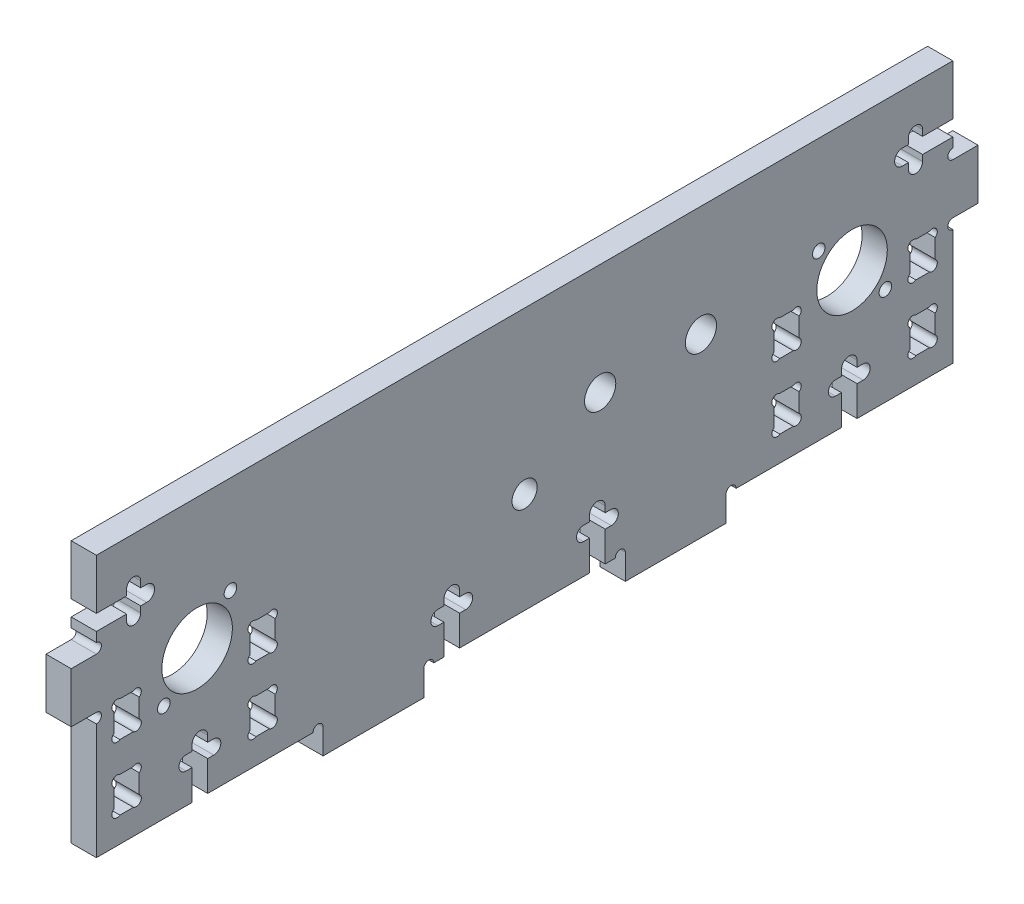
SolidWorks part; units mm, degrees
ref_plane "정면" through (0, 0, 0) normal (0, 0, 1) x (1, 0, 0)
ref_plane "윗면" through (0, 0, 0) normal (0, 1, 0) x (1, 0, 0)
ref_plane "우측면" through (0, 0, 0) normal (1, 0, 0) x (0, 0, -1)
sketch "스케치1" plane through (0, 0, 0) normal (1, 0, 0) x (0, 0, -1)
  line L1 (0, 0) -> (170, 0)
  line L2 (0, 0) -> (0, 52)
  line L3 (0, 52) -> (170, 52)
  line L4 (170, 0) -> (170, 52)
  dimension "D1" = 170
  dimension "D2" = 52
extrude "보스-돌출1" add sketch "스케치1" along normal blind 5
sketch "스케치2" plane through (5, 0, 0) normal (1, 0, 0) x (0, 0, -1)
  line L0 (170, 26) -> (150, 26) construction
  line L1 (170, 0) -> (170, 52) construction
  line L2 (150, 26) -> (20, 26) construction
  line L3 (20, 26) -> (0, 26) construction
  line L4 (0, 52) -> (0, 0) construction
  circle A0 centre (150, 26) radius 7
  circle A1 centre (20, 26) radius 7
  dimension "D2" = 14
  dimension "D1" = 20
extrude "컷-돌출1" cut sketch "스케치2" against normal blind 10
sketch "스케치3" plane through (5, 0, 0) normal (1, 0, 0) x (0, 0, -1)
  line L0 (0, 0) -> (170, 0) construction
  line L1 (45, 0) -> (65, 0)
  line L2 (45, 0) -> (45, -5)
  line L3 (45, -5) -> (65, -5)
  line L4 (65, 0) -> (65, -5)
  line L5 (0, -5) -> (45, -5) construction
  line L6 (65, -5) -> (105, -5) construction
  line L7 (125, 0) -> (105, 0)
  line L8 (125, 0) -> (125, -5)
  line L9 (125, -5) -> (105, -5)
  line L10 (105, 0) -> (105, -5)
  line L11 (125, -5) -> (170, -5) construction
  line L12 (170, -5) -> (170, 0) construction
  line L13 (0, 0) -> (0, -5) construction
  line L14 (0, 0) -> (0, -5) construction
  line L15 (0, -5) -> (45, -5) construction
  dimension "D1" = 45
  dimension "D2" = 20
extrude "보스-돌출2" add sketch "스케치3" against normal blind 5
sketch "스케치6" plane through (5, 0, 0) normal (1, 0, 0) x (0, 0, -1)
  line L0 (151, 0) -> (151, 6)
  line L1 (147.9, 10) -> (151, 10) construction
  line L2 (146.7, 6) -> (146.7, 8.8) construction
  line L3 (151, 6) -> (151, 8.8) construction
  line L4 (147.9, 0) -> (151, 0)
  line L5 (146.7, 8.8) -> (147.9, 8.8)
  line L6 (147.9, 0) -> (147.9, 6)
  line L7 (152.2, 8.8) -> (152.2, 6) construction
  line L8 (147.9, 6) -> (146.7, 6)
  line L9 (147.9, 8.8) -> (147.9, 6) construction
  line L10 (151, 8.8) -> (151, 10)
  line L11 (147.9, 6) -> (151, 6) construction
  line L12 (147.9, 8.8) -> (151, 8.8) construction
  line L13 (151, 8.8) -> (152.2, 8.8)
  line L14 (147.9, 8.8) -> (147.9, 10)
  line L15 (149.45, 10) -> (149.45, 12.1831) construction
  line L16 (152.2, 6) -> (151, 6)
  line L18 (65, 0) -> (105, 0) construction
  line L19 (101, 0) -> (101, 6)
  line L20 (97.9, 10) -> (101, 10) construction
  line L21 (96.7, 6) -> (96.7, 8.8) construction
  line L22 (101, 6) -> (101, 8.8) construction
  line L23 (97.9, 0) -> (101, 0)
  line L24 (96.7, 8.8) -> (97.9, 8.8)
  line L25 (97.9, 0) -> (97.9, 6)
  line L26 (102.2, 8.8) -> (102.2, 6) construction
  line L27 (97.9, 6) -> (96.7, 6)
  line L28 (97.9, 8.8) -> (97.9, 6) construction
  line L29 (101, 8.8) -> (101, 10)
  line L30 (97.9, 6) -> (101, 6) construction
  line L31 (97.9, 8.8) -> (101, 8.8) construction
  line L32 (101, 8.8) -> (102.2, 8.8)
  line L33 (97.9, 8.8) -> (97.9, 10)
  line L34 (99.45, 10) -> (99.45, 12.1831) construction
  line L35 (102.2, 6) -> (101, 6)
  line L37 (105, 0) -> (105, -5) construction
  line L71 (85, 52) -> (85, 0) construction
  line L72 (170, 52) -> (0, 52) construction
  line L89 (70.55, 10) -> (70.55, 12.1831) construction
  line L90 (72.1, 8.8) -> (69, 8.8) construction
  line L91 (72.1, 6) -> (69, 6) construction
  line L92 (72.1, 8.8) -> (72.1, 6) construction
  line L93 (67.8, 8.8) -> (67.8, 6) construction
  line L94 (69, 6) -> (69, 8.8) construction
  line L95 (73.3, 6) -> (73.3, 8.8) construction
  line L96 (72.1, 10) -> (69, 10) construction
  line L97 (20.55, 10) -> (20.55, 12.1831) construction
  line L98 (22.1, 8.8) -> (19, 8.8) construction
  line L99 (22.1, 6) -> (19, 6) construction
  line L100 (22.1, 8.8) -> (22.1, 6) construction
  line L101 (17.8, 8.8) -> (17.8, 6) construction
  line L102 (19, 6) -> (19, 8.8) construction
  line L103 (23.3, 6) -> (23.3, 8.8) construction
  line L104 (22.1, 10) -> (19, 10) construction
  line L123 (67.8, 6) -> (69, 6)
  line L124 (72.1, 8.8) -> (72.1, 10)
  line L125 (69, 8.8) -> (67.8, 8.8)
  line L126 (69, 8.8) -> (69, 10)
  line L127 (72.1, 6) -> (73.3, 6)
  line L128 (72.1, 0) -> (72.1, 6)
  line L129 (73.3, 8.8) -> (72.1, 8.8)
  line L130 (72.1, 0) -> (69, 0)
  line L131 (69, 0) -> (69, 6)
  line L132 (17.8, 6) -> (19, 6)
  line L133 (22.1, 8.8) -> (22.1, 10)
  line L134 (19, 8.8) -> (17.8, 8.8)
  line L135 (19, 8.8) -> (19, 10)
  line L136 (22.1, 6) -> (23.3, 6)
  line L137 (22.1, 0) -> (22.1, 6)
  line L138 (23.3, 8.8) -> (22.1, 8.8)
  line L139 (22.1, 0) -> (19, 0)
  line L140 (19, 0) -> (19, 6)
  arc A0 (151, 10) -> (147.9, 10) centre (149.45, 10) ccw
  arc A1 (146.7, 8.8) -> (146.7, 6) centre (146.7, 7.4) ccw
  arc A2 (152.2, 6) -> (152.2, 8.8) centre (152.2, 7.4) ccw
  arc A3 (101, 10) -> (97.9, 10) centre (99.45, 10) ccw
  arc A4 (96.7, 8.8) -> (96.7, 6) centre (96.7, 7.4) ccw
  arc A5 (102.2, 6) -> (102.2, 8.8) centre (102.2, 7.4) ccw
  arc A18 (67.8, 6) -> (67.8, 8.8) centre (67.8, 7.4) cw
  arc A19 (73.3, 8.8) -> (73.3, 6) centre (73.3, 7.4) cw
  arc A20 (69, 10) -> (72.1, 10) centre (70.55, 10) cw
  arc A21 (17.8, 6) -> (17.8, 8.8) centre (17.8, 7.4) cw
  arc A22 (23.3, 8.8) -> (23.3, 6) centre (23.3, 7.4) cw
  arc A23 (19, 10) -> (22.1, 10) centre (20.55, 10) cw
  dimension "D1" = 3.1
  dimension "D2" = 4
  dimension "D3" = 5.5
  dimension "D4" = 2.8
  dimension "D7" = 3.1
  dimension "D9" = 5.5
  dimension "D10" = 2.8
  dimension "D12" = 50
extrude "컷-돌출2" cut sketch "스케치6" against normal blind 10
sketch "스케치8" plane through (5, 0, 0) normal (1, 0, 0) x (0, 0, -1)
  line L0 (170, 0) -> (170, 52) construction
  line L1 (170, 35) -> (175, 35)
  line L2 (170, 35) -> (170, 25)
  line L3 (170, 25) -> (175, 25)
  line L4 (175, 35) -> (175, 25)
  line L5 (175, 52) -> (175, 35) construction
  line L8 (85, 0) -> (85, 52) construction
  line L9 (72.1, 0) -> (97.9, 0) construction
  line L10 (170, 52) -> (0, 52) construction
  line L11 (-5, 35) -> (-5, 25)
  line L12 (0, 25) -> (-5, 25)
  line L13 (0, 35) -> (0, 25)
  line L14 (0, 35) -> (-5, 35)
  line L15 (151, 0) -> (170, 0) construction
  dimension "D1" = 25
  dimension "D2" = 10
extrude "보스-돌출3" add sketch "스케치8" against normal blind 5
sketch "스케치7" plane through (5, 0, 0) normal (1, 0, 0) x (0, 0, -1)
  line L0 (65, 0) -> (69, 0) construction
  line L1 (22.1, 0) -> (45, 0) construction
  line L2 (101, 0) -> (105, 0) construction
  line L3 (125, 0) -> (147.9, 0) construction
  line L4 (170, 35) -> (170, 52) construction
  line L5 (170, 0) -> (170, 25) construction
  line L6 (0, 52) -> (0, 35) construction
  line L7 (0, 25) -> (0, 0) construction
  circle A0 centre (66, 0) radius 1
  circle A1 centre (44, 0) radius 1
  circle A2 centre (104, 0) radius 1
  circle A3 centre (126, 0) radius 1
  circle A4 centre (170, 36) radius 1
  circle A5 centre (170, 24) radius 1
  circle A6 centre (0, 36) radius 1
  circle A7 centre (0, 24) radius 1
  dimension "D1" = 2
extrude "컷-돌출3" cut sketch "스케치7" against normal blind 10
sketch "스케치10" plane through (0, 0, 0) normal (-1, 0, 0) x (0, 0, 1)
  line L0 (-166.5, 25) -> (-161.5, 18) construction
  line L1 (-166.5, 18) -> (-161.5, 18)
  line L2 (-166.5, 18) -> (-166.5, 25)
  line L3 (-166.5, 25) -> (-161.5, 25)
  line L4 (-161.5, 18) -> (-161.5, 25)
  line L5 (-161.5, 25) -> (-166.5, 18) construction
  line L6 (-85, 52) -> (-85, 0) construction
  line L7 (-139.5, 18) -> (-134.5, 18)
  line L8 (-139.5, 18) -> (-139.5, 25)
  line L9 (-139.5, 25) -> (-134.5, 25)
  line L10 (-134.5, 18) -> (-134.5, 25)
  line L11 (-166.5, 5) -> (-161.5, 5)
  line L12 (-166.5, 5) -> (-166.5, 12)
  line L13 (-166.5, 12) -> (-161.5, 12)
  line L14 (-161.5, 5) -> (-161.5, 12)
  line L15 (-139.5, 12) -> (-134.5, 12)
  line L16 (-139.5, 12) -> (-139.5, 5)
  line L17 (-139.5, 5) -> (-134.5, 5)
  line L18 (-134.5, 12) -> (-134.5, 5)
  line L19 (-170, 52) -> (0, 52) construction
  line L20 (-72.1, 0) -> (-97.9, 0) construction
  line L21 (-8.5, 25) -> (-3.5, 18) construction
  line L22 (-3.5, 25) -> (-8.5, 18) construction
  line L23 (-35.5, 12) -> (-35.5, 5)
  line L24 (-30.5, 5) -> (-35.5, 5)
  line L25 (-30.5, 12) -> (-30.5, 5)
  line L26 (-30.5, 12) -> (-35.5, 12)
  line L27 (-8.5, 5) -> (-8.5, 12)
  line L28 (-3.5, 12) -> (-8.5, 12)
  line L29 (-3.5, 5) -> (-3.5, 12)
  line L30 (-3.5, 5) -> (-8.5, 5)
  line L31 (-35.5, 18) -> (-35.5, 25)
  line L32 (-30.5, 25) -> (-35.5, 25)
  line L33 (-30.5, 18) -> (-30.5, 25)
  line L34 (-30.5, 18) -> (-35.5, 18)
  line L35 (-8.5, 18) -> (-8.5, 25)
  line L36 (-3.5, 25) -> (-8.5, 25)
  line L37 (-3.5, 18) -> (-3.5, 25)
  line L38 (-3.5, 18) -> (-8.5, 18)
extrude "컷-돌출4" cut sketch "스케치10" against normal blind 10
sketch "스케치11" plane through (5, 0, 0) normal (1, 0, 0) x (0, 0, -1)
  line L0 (85, 52) -> (85, 0) construction
  line L1 (170, 52) -> (0, 52) construction
  line L2 (72.1, 0) -> (97.9, 0) construction
  line L3 (161.5, 25) -> (166.5, 18) construction
  line L4 (166.5, 25) -> (161.5, 18) construction
  line L5 (139.5, 18) -> (161.5, 18) construction
  line L6 (161.5, 18) -> (161.5, 12) construction
  line L7 (161.5, 12) -> (139.5, 12) construction
  line L8 (139.5, 12) -> (139.5, 18) construction
  line L9 (150.5, 18) -> (150.5, 12) construction
  line L10 (139.5, 15) -> (161.5, 15) construction
  line L11 (134.5, 25) -> (139.5, 18) construction
  line L12 (139.5, 25) -> (134.5, 18) construction
  line L13 (139.5, 5) -> (134.5, 12) construction
  line L14 (134.5, 5) -> (139.5, 12) construction
  line L15 (166.5, 5) -> (161.5, 12) construction
  line L16 (161.5, 5) -> (166.5, 12) construction
  line L17 (8.5, 5) -> (3.5, 12) construction
  line L18 (3.5, 5) -> (8.5, 12) construction
  line L19 (35.5, 5) -> (30.5, 12) construction
  line L20 (30.5, 5) -> (35.5, 12) construction
  line L21 (30.5, 25) -> (35.5, 18) construction
  line L22 (35.5, 25) -> (30.5, 18) construction
  line L23 (30.5, 15) -> (8.5, 15) construction
  line L24 (19.5, 18) -> (19.5, 12) construction
  line L25 (30.5, 12) -> (30.5, 18) construction
  line L26 (8.5, 12) -> (30.5, 12) construction
  line L27 (8.5, 18) -> (8.5, 12) construction
  line L28 (30.5, 18) -> (8.5, 18) construction
  line L29 (3.5, 25) -> (8.5, 18) construction
  line L30 (8.5, 25) -> (3.5, 18) construction
  circle A0 centre (165.9188, 24.1863) radius 1
  circle A1 centre (162.0812, 24.1863) radius 1
  circle A2 centre (165.9188, 18.8137) radius 1
  circle A3 centre (162.0812, 18.8137) radius 1
  circle A4 centre (138.9188, 18.8137) radius 1
  circle A5 centre (135.0812, 18.8137) radius 1
  circle A6 centre (138.9188, 24.1863) radius 1
  circle A7 centre (135.0812, 24.1863) radius 1
  circle A8 centre (135.0812, 5.8137) radius 1
  circle A9 centre (138.9188, 5.8137) radius 1
  circle A10 centre (135.0812, 11.1863) radius 1
  circle A11 centre (138.9188, 11.1863) radius 1
  circle A12 centre (162.0812, 11.1863) radius 1
  circle A13 centre (165.9188, 11.1863) radius 1
  circle A14 centre (162.0812, 5.8137) radius 1
  circle A15 centre (165.9188, 5.8137) radius 1
  circle A16 centre (4.0812, 5.8137) radius 1
  circle A17 centre (7.9188, 5.8137) radius 1
  circle A18 centre (4.0812, 11.1863) radius 1
  circle A19 centre (7.9188, 11.1863) radius 1
  circle A20 centre (31.0812, 11.1863) radius 1
  circle A21 centre (34.9188, 11.1863) radius 1
  circle A22 centre (31.0812, 5.8137) radius 1
  circle A23 centre (34.9188, 5.8137) radius 1
  circle A24 centre (34.9188, 24.1863) radius 1
  circle A25 centre (31.0812, 24.1863) radius 1
  circle A26 centre (34.9188, 18.8137) radius 1
  circle A27 centre (31.0812, 18.8137) radius 1
  circle A28 centre (7.9188, 18.8137) radius 1
  circle A29 centre (4.0812, 18.8137) radius 1
  circle A30 centre (7.9188, 24.1863) radius 1
  circle A31 centre (4.0812, 24.1863) radius 1
  dimension "D1" = 2
extrude "컷-돌출5" cut sketch "스케치11" against normal blind 10
sketch "스케치12" plane through (5, 0, 0) normal (1, 0, 0) x (0, 0, -1)
  line L0 (170, 42) -> (164, 42)
  line L1 (160, 38.9) -> (160, 42) construction
  line L2 (164, 37.7) -> (161.2, 37.7) construction
  line L3 (164, 42) -> (161.2, 42) construction
  line L4 (170, 38.9) -> (170, 42)
  line L5 (161.2, 37.7) -> (161.2, 38.9)
  line L6 (170, 38.9) -> (164, 38.9)
  line L7 (161.2, 43.2) -> (164, 43.2) construction
  line L8 (164, 38.9) -> (164, 37.7)
  line L9 (161.2, 38.9) -> (164, 38.9) construction
  line L10 (161.2, 42) -> (160, 42)
  line L11 (164, 38.9) -> (164, 42) construction
  line L12 (161.2, 38.9) -> (161.2, 42) construction
  line L13 (161.2, 42) -> (161.2, 43.2)
  line L14 (161.2, 38.9) -> (160, 38.9)
  line L15 (160, 40.45) -> (158.45, 40.45) construction
  line L16 (164, 43.2) -> (164, 42)
  line L17 (162.6, 37.7) -> (162.6, 38.9) construction
  line L18 (162.6, 43.2) -> (162.6, 42) construction
  line L19 (161.2, 40.45) -> (160, 40.45) construction
  line L20 (162.6, 43.2) -> (162.6, 44.6) construction
  line L21 (162.6, 37.7) -> (162.6, 36.3) construction
  line L22 (170, 37) -> (170, 52) construction
  line L23 (170, 52) -> (0, 52) construction
  line L24 (85, 52) -> (85, 0) construction
  line L25 (72.1, 0) -> (97.9, 0) construction
  line L26 (7.4, 37.7) -> (7.4, 36.3) construction
  line L27 (7.4, 43.2) -> (7.4, 44.6) construction
  line L28 (8.8, 40.45) -> (10, 40.45) construction
  line L29 (7.4, 43.2) -> (7.4, 42) construction
  line L30 (7.4, 37.7) -> (7.4, 38.9) construction
  line L31 (10, 40.45) -> (11.55, 40.45) construction
  line L32 (8.8, 38.9) -> (8.8, 42) construction
  line L33 (6, 38.9) -> (6, 42) construction
  line L34 (8.8, 38.9) -> (6, 38.9) construction
  line L35 (8.8, 43.2) -> (6, 43.2) construction
  line L36 (6, 42) -> (8.8, 42) construction
  line L37 (6, 37.7) -> (8.8, 37.7) construction
  line L38 (10, 38.9) -> (10, 42) construction
  line L39 (6, 43.2) -> (6, 42)
  line L40 (8.8, 38.9) -> (10, 38.9)
  line L41 (8.8, 42) -> (8.8, 43.2)
  line L42 (8.8, 42) -> (10, 42)
  line L43 (6, 38.9) -> (6, 37.7)
  line L44 (0, 38.9) -> (6, 38.9)
  line L45 (8.8, 37.7) -> (8.8, 38.9)
  line L46 (0, 38.9) -> (0, 42)
  line L47 (0, 42) -> (6, 42)
  arc A0 (160, 42) -> (160, 38.9) centre (160, 40.45) ccw
  arc A1 (161.2, 37.7) -> (164, 37.7) centre (162.6, 37.7) ccw
  arc A2 (164, 43.2) -> (161.2, 43.2) centre (162.6, 43.2) ccw
  arc A3 (6, 43.2) -> (8.8, 43.2) centre (7.4, 43.2) cw
  arc A4 (8.8, 37.7) -> (6, 37.7) centre (7.4, 37.7) cw
  arc A5 (10, 42) -> (10, 38.9) centre (10, 40.45) cw
  dimension "D1" = 3.1
  dimension "D2" = 5.5
  dimension "D3" = 2.8
  dimension "D4" = 1.2
  dimension "D5" = 10
  dimension "D6" = 3.1
extrude "컷-돌출6" cut sketch "스케치12" against normal blind 10
sketch "스케치13" plane through (5, 0, 0) normal (1, 0, 0) x (0, 0, -1)
  line L0 (120, 30) -> (100, 30) construction
  line L1 (127, 0) -> (147.9, 0) construction
  line L2 (170, 37) -> (170, 38.9) construction
  line L3 (72.1, 0) -> (97.9, 0) construction
  circle A0 centre (100, 30) radius 3.1
  circle A1 centre (120, 30) radius 3.1
  circle A2 centre (85, 20) radius 2.5
  dimension "D1" = 6.2
  dimension "D5" = 20
  dimension "D6" = 5
  dimension "D2" = 20
  dimension "D3" = 30
  dimension "D4" = 50
extrude "컷-돌출7" cut sketch "스케치13" against normal blind 10
sketch "스케치14" plane through (5, 0, 0) normal (1, 0, 0) x (0, 0, -1)
  line L0 (150, 26) -> (155.6569, 20.3431) construction
  line L1 (155.6569, 20.3431) -> (156.6114, 19.3886) construction
  line L2 (150, 26) -> (150, 14.9084) construction
  line L3 (150, 26) -> (155.6569, 31.6569) construction
  line L4 (85, 52) -> (85, 0) construction
  line L5 (170, 52) -> (0, 52) construction
  line L6 (72.1, 0) -> (97.9, 0) construction
  circle A1 centre (150, 26) radius 8 construction
  circle A2 centre (156.6114, 19.3886) radius 1.25
  circle A3 centre (143.3886, 32.6114) radius 1.25
  circle A4 centre (13.3886, 19.3886) radius 1.25
  circle A5 centre (26.6114, 32.6114) radius 1.25
  dimension "D1" = 2.5
  dimension "D2" = 1.35
  dimension "D3" = 45
extrude "컷-돌출8" cut sketch "스케치14" against normal blind 10
